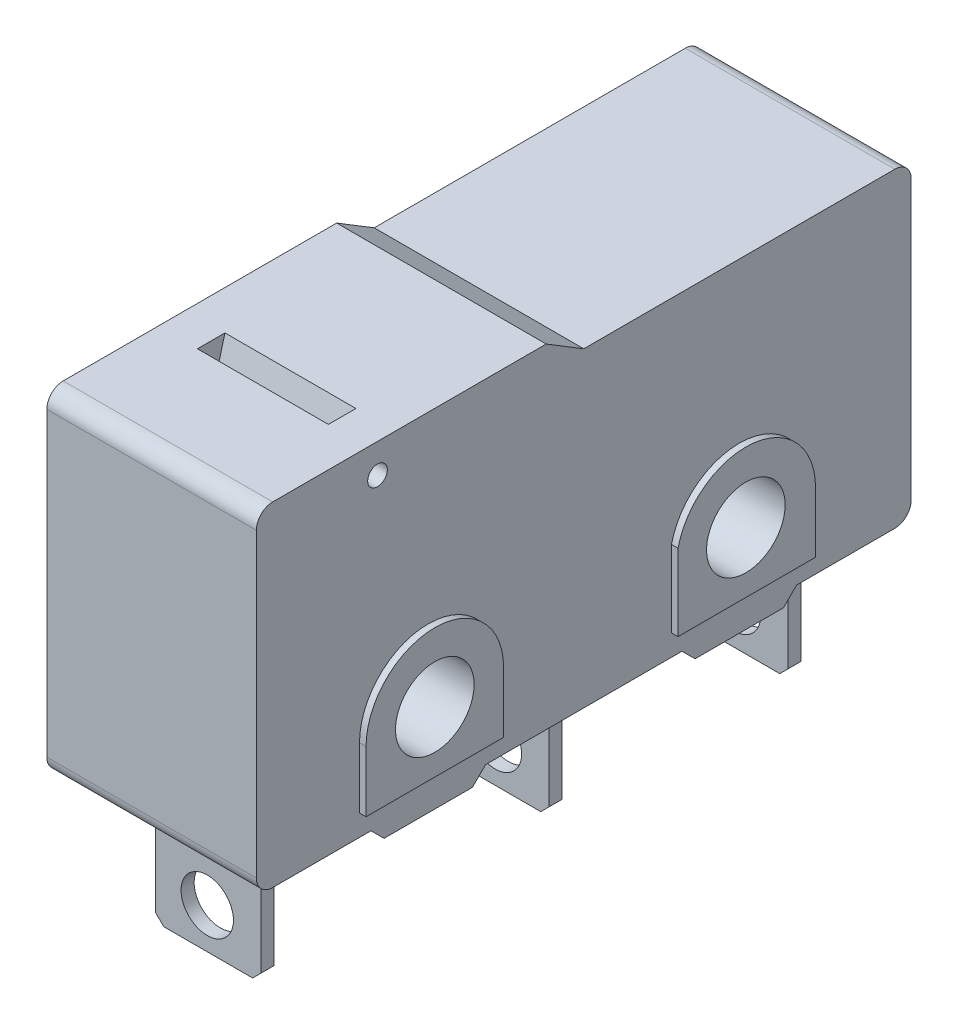
SolidWorks part; units mm, degrees
ref_plane "Front Plane" through (0, 0, 0) normal (0, 0, 1) x (1, 0, 0)
ref_plane "Top Plane" through (0, 0, 0) normal (0, 1, 0) x (1, 0, 0)
ref_plane "Right Plane" through (0, 0, 0) normal (1, 0, 0) x (0, 0, -1)
sketch "Sketch1" plane through (0, 0, 0) normal (1, 0, 0) x (0, 0, -1)
  line L0 (10, 4.4) -> (0, 4.4)
  line L2 (10, 4.4) -> (10, -5.1)
  line L4 (-10, 5.1) -> (-10, -5.1)
  line L5 (0, 4.4) -> (-1.1476, 5.1)
  line L6 (10, -5.1) -> (-10, 5.1) construction
  line L7 (-1.1476, 5.1) -> (-10, 5.1)
  line L8 (-10, -5.1) -> (-6.5, -5.1)
  line L12 (-3, -5.1) -> (3, -5.1)
  line L16 (6.5, -5.1) -> (10, -5.1)
  line L17 (-6.5, -5.1) -> (-6.1, -5.5)
  line L18 (-6.1, -5.5) -> (-3.4, -5.5)
  line L19 (-3.4, -5.5) -> (-3, -5.1)
  line L20 (6.5, -5.1) -> (6.1, -5.5)
  line L21 (3, -5.1) -> (3.4, -5.5)
  line L23 (3.4, -5.5) -> (6.1, -5.5)
  point P0 (0, 0)
  dimension "D1" = 20
  dimension "D2" = 10.2
  dimension "D3" = 9.5
  dimension "D4" = 20
  dimension "D5" = 3.5
  dimension "D6" = 0.4
  dimension "D7" = 45
  dimension "D8" = 45
  dimension "D9" = 45
  dimension "D10" = 0.4
  dimension "D11" = 45
  dimension "D12" = 6
extrude "Boss-Extrude1" add sketch "Sketch1" along normal mid plane 6.4
sketch "Sketch5" plane through (0, -5.1, 0) normal (0, -1, 0) x (1, 0, 0)
  line L0 (-1.5777, 8.3) -> (1.6361, 8.3)
  line L1 (1.6361, 8.3) -> (1.6361, 7.9)
  line L2 (1.6361, 7.9) -> (-1.5777, 7.9)
  line L3 (-1.5777, 7.9) -> (-1.5777, 8.3)
  line L4 (-1.5777, -0.5) -> (1.6361, -0.5)
  line L5 (1.6361, -0.5) -> (1.6361, -0.9)
  line L6 (1.6361, -0.9) -> (-1.5777, -0.9)
  line L7 (-1.5777, -0.9) -> (-1.5777, -0.5)
  line L8 (-1.5777, -7.8) -> (1.6361, -7.8)
  line L9 (1.6361, -7.8) -> (1.6361, -8.2)
  line L10 (1.6361, -8.2) -> (-1.5777, -8.2)
  line L11 (-1.5777, -8.2) -> (-1.5777, -7.8)
  line L12 (3.2, 10) -> (-3.2, 10) construction
  point P10 (-1.5777, -0.7)
  point P13 (-1.5777, 8.1)
  point P14 (1.6361, 8.1)
  dimension "D1" = 1.7
  dimension "D2" = 0.4
  dimension "D3" = 8.8
  dimension "D4" = 7.3
extrude "Boss-Extrude2" add sketch "Sketch5" along normal blind 3.9
chamfer "Chamfer2" distance 0.25 angle 45 6 edges at (-1.5777, -9, 8.1) (1.6361, -9, -8) (-1.5777, -9, -8) (1.6361, -9, -0.7) (-1.5777, -9, -0.7) (1.6361, -9, 8.1)
sketch "Sketch6" plane through (0, 0, 8.3) normal (0, 0, 1) x (1, 0, 0)
  line L0 (0, -55) -> (0, 55) construction
  circle A0 centre (0, -7.7687) radius 0.8
  point P4 (0, -7.5216)
  point P5 (0, -7.7687)
  dimension "D1" = 1.6
extrude "Cut-Extrude1" cut sketch "Sketch6" against normal through all
fillet "Fillet1" radius 0.5 4 edges at (0, -5.1, -10) (0, 4.4, -10) (0, -5.1, 10) (0, 5.1, 10)
sketch "Sketch7" plane through (3.2, 0, 0) normal (1, 0, 0) x (0, 0, -1)
  line L0 (-10, 4.6) -> (-10, -4.6) construction
  line L1 (-9.5, -5.1) -> (-6.5, -5.1) construction
  circle A0 centre (-4.75, -2.6) radius 1.2
  circle A1 centre (4.75, -2.6) radius 1.2
  dimension "D3" = 2.4
  dimension "D1" = 5.25
  dimension "D2" = 9.5
  dimension "D4" = 2.5
extrude "Cut-Extrude2" cut sketch "Sketch7" against normal through all
sketch "Sketch11" plane through (0, 0, 0) normal (1, 0, 0) x (0, 0, -1)
  line L0 (-6.85, -4.4534) -> (-2.65, -4.4534)
  line L1 (-2.65, -4.4534) -> (-2.65, -2.6)
  line L2 (-6.85, -2.6) -> (-6.85, -4.4534)
  line L3 (2.6782, -4.4534) -> (6.8782, -4.4534)
  line L4 (6.8782, -4.4534) -> (6.8782, -2.6)
  line L5 (2.6782, -2.1134) -> (2.6782, -4.4534)
  circle A0 centre (-4.75, -2.6) radius 1.2
  circle A1 centre (4.75, -2.6) radius 1.2
  arc A2 (-2.65, -2.6) -> (-6.85, -2.6) centre (-4.75, -2.6) ccw
  arc A3 (6.8782, -2.6) -> (2.6782, -2.1134) centre (4.75, -2.6) ccw
  dimension "D1" = 4.2
extrude "Boss-Extrude5" add sketch "Sketch11" along normal blind 3.4 and the other way blind 3.4
sketch "Sketch12" plane through (3.2, 0, 0) normal (1, 0, 0) x (0, 0, -1)
  line L0 (10, -4.6) -> (10, 3.9) construction
  circle A0 centre (-6.3, 4.202) radius 0.3
  dimension "D1" = 0.6
  dimension "D2" = 16.3
extrude "Cut-Extrude3" cut sketch "Sketch12" against normal through all
sketch "Sketch13" plane through (0, 0, 0) normal (1, 0, 0) x (0, 0, -1)
  line L0 (-6.6, 4.202) -> (-6.6, 5.1)
  line L1 (-1.1476, 5.1) -> (-9.5, 5.1) construction
  line L2 (-6.6, 5.1) -> (-5.7594, 5.1)
  line L3 (-5.7594, 5.1) -> (-6, 4.202)
  line L4 (-6, 4.202) -> (-6.6, 4.202)
  circle A0 centre (-6.3, 4.202) radius 0.3 construction
  point P10 (0, 0)
  point P11 (-4.4332, 6.4868)
  dimension "D1" = 75
extrude "Cut-Extrude4" cut sketch "Sketch13" against normal blind 2 and the other way blind 2
